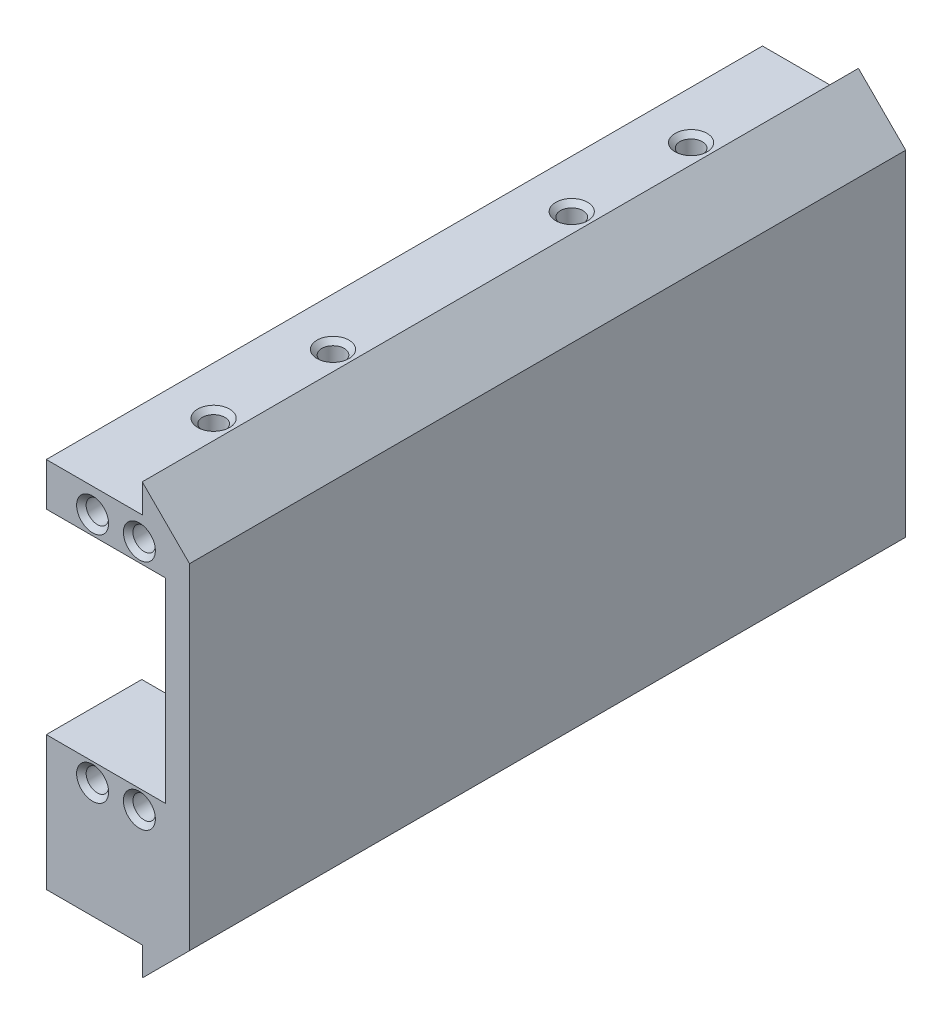
SolidWorks part; units mm, degrees
material "ABS"
ref_plane "Front Plane" through (0, 0, 0) normal (0, 0, 1) x (1, 0, 0)
ref_plane "Top Plane" through (0, 0, 0) normal (0, 1, 0) x (1, 0, 0)
ref_plane "Right Plane" through (0, 0, 0) normal (1, 0, 0) x (0, 0, -1)
sketch "Sketch1" plane through (0, 0, 0) normal (0, 0, 1) x (1, 0, 0)
  line L0 (-15, 45) -> (15, 45)
  line L1 (-15, 45) -> (15, 45) construction
  line L2 (-15, 45) -> (-15, -45) construction
  line L3 (-15, -45) -> (15, -45) construction
  line L4 (15, 45) -> (15, -45) construction
  line L5 (-15, 45) -> (15, -45) construction
  line L6 (-15, -45) -> (15, 45) construction
  line L7 (15, 45) -> (15, -45)
  line L8 (15, -45) -> (-15, -45)
  line L9 (-15, -45) -> (-15, -10.9)
  line L10 (-15, -10.9) -> (10, -10.9)
  line L11 (10, -10.9) -> (10, 30)
  line L12 (10, 30) -> (-15, 30)
  line L13 (-15, 30) -> (-15, 45)
  point P0 (0, 0)
  dimension "D1" = 90
  dimension "D2" = 30
  dimension "D3" = 40.9
  dimension "D4" = 15
  dimension "D5" = 5
extrude "Boss-Extrude1" add sketch "Sketch1" along normal blind 150
sketch "Sketch2" plane through (0, 0, 150) normal (0, 0, 1) x (1, 0, 0)
  line L0 (10, 30) -> (-10.8, 30) construction
  line L1 (-15, 30) -> (10, 30) construction
  line L2 (-0.4, 30) -> (-0.4, 33.89) construction
  line L3 (-0.4, 33.89) -> (4.5, 33.89) construction
  line L4 (10, 30) -> (10, -10.9) construction
  line L5 (10, 9.55) -> (15, 9.55) construction
  line L7 (15, -45) -> (15, 45) construction
  circle A0 centre (4.5, 33.89) radius 2.35
  circle A1 centre (-5.3, 33.89) radius 2.35
  circle A4 centre (4.5, -14.79) radius 2.35
  circle A5 centre (-5.3, -14.79) radius 2.35
  dimension "D4" = 4.7
  dimension "D1" = 20.8
  dimension "D2" = 3.89
  dimension "D3" = 4.9
extrude "Cut-Extrude1" cut sketch "Sketch2" against normal blind 8
sketch "Sketch3" plane through (0, 0, 0) normal (0, 0, -1) x (-1, 0, 0)
  line L0 (-10, 30) -> (10.8, 30) construction
  line L1 (15, 30) -> (-10, 30) construction
  line L2 (-10, 30) -> (-10, -10.9) construction
  line L3 (-10, 9.55) -> (-15, 9.55) construction
  line L5 (0.4, 30) -> (0.4, 33.89) construction
  line L6 (0.4, 33.89) -> (-4.5, 33.89) construction
  line L7 (-15, -45) -> (-15, 45) construction
  circle A0 centre (-4.5, 33.89) radius 2.35
  circle A1 centre (5.3, 33.89) radius 2.35
  circle A4 centre (-4.5, -14.79) radius 2.35
  circle A5 centre (5.3, -14.79) radius 2.35
  dimension "D4" = 4.7
  dimension "D1" = 20.8
  dimension "D2" = 3.89
  dimension "D3" = 4.9
extrude "Cut-Extrude2" cut sketch "Sketch3" against normal blind 8
chamfer "Chamfer1" distance 1 angle 45 8 edges at (2.15, 33.89, 0) (-2.95, 33.89, 0) (-7.65, 33.89, 150) (6.85, 33.89, 150) (2.15, -14.79, 150) (-2.95, -14.79, 150) (-7.65, -14.79, 0) (6.85, -14.79, 0)
sketch "Sketch4" plane through (0, 0, 150) normal (0, 0, 1) x (1, 0, 0)
  line L0 (0, 0) -> (15, 0) construction
  line L1 (-15, -45) -> (5.1, -45)
  line L2 (-15, -45) -> (-15, -39)
  line L3 (-15, -39) -> (5.1, -39)
  line L4 (5.1, -45) -> (5.1, -39)
  line L5 (15, -45) -> (15, 45) construction
  line L6 (-15, 39) -> (5.1, 39)
  line L7 (5.1, 45) -> (5.1, 39)
  line L8 (-15, 45) -> (5.1, 45)
  line L9 (-15, 45) -> (-15, 39)
  dimension "D1" = 6
  dimension "D2" = 20.1
extrude "Cut-Extrude3" cut sketch "Sketch4" against normal through all
chamfer "Chamfer2" distance 9.9 angle 45 2 edges at (15, -45, 75) (15, 45, 75)
sketch "Sketch5" plane through (0, 39, 0) normal (0, 1, 0) x (1, 0, 0)
  line L0 (-4.95, 0) -> (-4.95, -25) construction
  line L1 (-15, 0) -> (5.1, 0) construction
  line L2 (-4.95, -25) -> (-4.95, -50) construction
  line L3 (-4.95, -50) -> (-4.95, -75) construction
  line L4 (-4.95, -100) -> (-4.95, -125) construction
  line L5 (-4.95, -125) -> (-4.95, -150) construction
  line L6 (-15, -150) -> (5.1, -150) construction
  line L8 (-4.95, -75) -> (-4.95, -100) construction
  line L10 (5.1, 0) -> (-15, 0) construction
  line L11 (5.1, 0) -> (5.1, -150) construction
  line L12 (5.1, -150) -> (-15, -150) construction
  line L13 (-15, 0) -> (-15, -150) construction
  circle A0 centre (-4.95, -25) radius 2.35
  circle A1 centre (-4.95, -50) radius 2.35
  circle A2 centre (-4.95, -100) radius 2.35
  circle A3 centre (-4.95, -125) radius 2.35
  dimension "D1" = 4.7
  dimension "D2" = 4.7
  dimension "D3" = 4.7
  dimension "D4" = 4.7
  dimension "D5" = 20.1
  dimension "D6" = 150
extrude "Cut-Extrude4" cut sketch "Sketch5" against normal blind 8
chamfer "Chamfer3" distance 1 angle 45 4 edges at (-4.95, 39, 127.35) (-4.95, 39, 102.35) (-4.95, 39, 52.35) (-4.95, 39, 27.35)
sketch "Sketch6" plane through (0, -39, 0) normal (0, -1, 0) x (1, 0, 0)
  line L1 (5, 121) -> (-15, 121) construction
  line L2 (5, 121) -> (5, 29) construction
  line L3 (5, 29) -> (-15, 29) construction
  line L4 (-15, 121) -> (-15, 29) construction
  line L5 (-15, 0) -> (-15, 150) construction
  line L6 (5.1, 150) -> (-15, 150) construction
  line L7 (5.1, 0) -> (-15, 0) construction
  line L8 (-5, 121) -> (-5, 90.3333) construction
  line L9 (-5, 90.3333) -> (-5, 59.6667) construction
  line L10 (-5, 59.6667) -> (-5, 29) construction
  circle A0 centre (-5, 59.6667) radius 4
  circle A1 centre (-5, 90.3333) radius 4
  dimension "D3" = 8
  dimension "D4" = 8
  dimension "D1" = 29
  dimension "D2" = 29
  dimension "D5" = 10
  dimension "D6" = 10
  dimension "D7" = 20
extrude "Cut-Extrude5" cut sketch "Sketch6" against normal blind 4.2
sketch "Sketch7" plane through (-15, 0, 0) normal (-1, 0, 0) x (0, 0, 1)
  line L0 (150, -39) -> (121, -39) construction
  line L1 (0, -39) -> (150, -39) construction
  line L2 (121, -39) -> (90.3333, -39) construction
  line L3 (90.3333, -39) -> (59.6667, -39) construction
  line L4 (59.6667, -39) -> (29, -39) construction
  line L5 (29, -39) -> (0, -39) construction
  line L6 (59.6667, -39) -> (59.6667, -34.8) construction
  line L7 (59.6667, -34.8) -> (90.3333, -34.8) construction
  line L8 (90.3333, -34.8) -> (90.3333, -39) construction
  line L9 (75, -34.8) -> (75, -39) construction
  line L10 (53.5167, -34.8) -> (65.8167, -34.8)
  line L11 (53.5167, -34.8) -> (53.5167, -38)
  line L12 (53.5167, -38) -> (65.8167, -38)
  line L13 (65.8167, -34.8) -> (65.8167, -38)
  line L14 (96.4833, -38) -> (84.1833, -38)
  line L15 (84.1833, -34.8) -> (84.1833, -38)
  line L16 (96.4833, -34.8) -> (84.1833, -34.8)
  line L17 (96.4833, -34.8) -> (96.4833, -38)
  point P17 (59.6667, -34.8)
  dimension "D1" = 29
  dimension "D2" = 29
  dimension "D3" = 4.2
  dimension "D4" = 3.2
  dimension "D5" = 12.3
extrude "Cut-Extrude6" cut sketch "Sketch7" against normal blind 16.1
sketch "Sketch8" plane through (-15, 0, 0) normal (-1, 0, 0) x (0, 0, 1)
  line L0 (150, -10.9) -> (130, -10.9) construction
  line L1 (150, -10.9) -> (0, -10.9) construction
  line L2 (0, -10.9) -> (20, -10.9) construction
  line L3 (150, -10.9) -> (0, -10.9) construction
  line L4 (65.8167, -34.8) -> (53.5167, -34.8) construction
  line L5 (20, -10.9) -> (130, -10.9)
  line L6 (20, -10.9) -> (20, -31.8)
  line L7 (20, -31.8) -> (130, -31.8)
  line L8 (130, -10.9) -> (130, -31.8)
  dimension "D1" = 20
  dimension "D2" = 20
  dimension "D3" = 3
extrude "Cut-Extrude7" cut sketch "Sketch8" against normal up to surface (25 mm away) up to face at (10, 9.55, 75)
